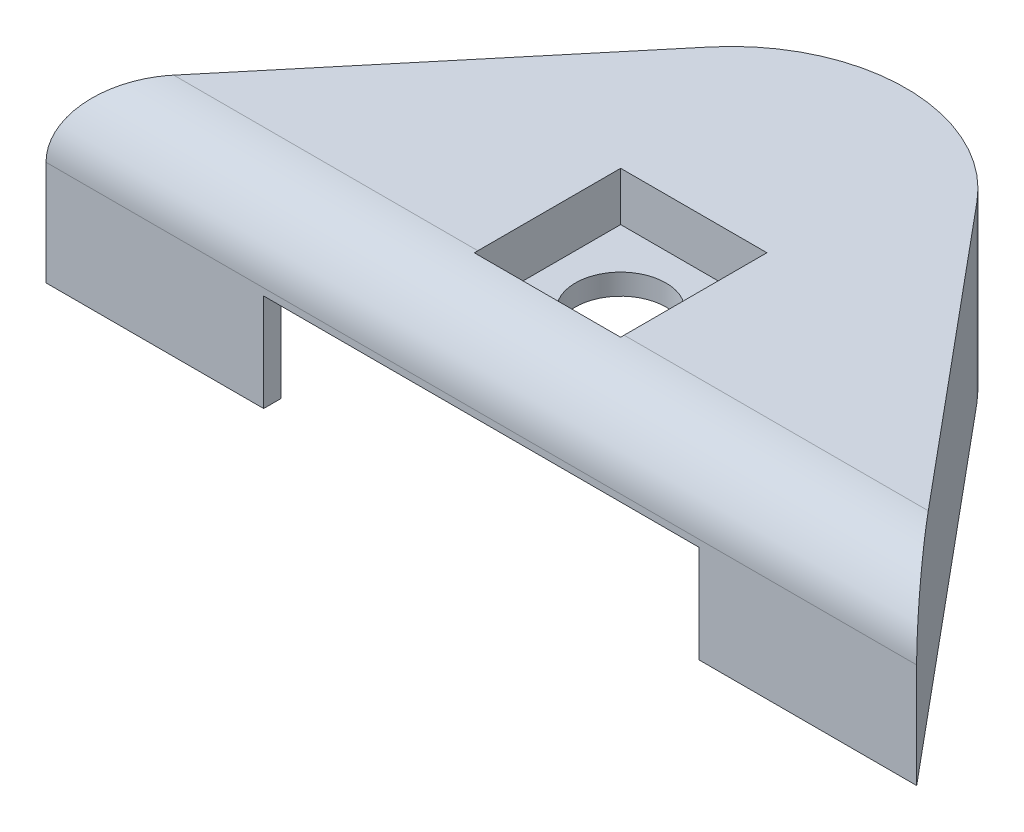
SolidWorks part; units mm, degrees
ref_plane "Ebene vorne" through (0, 0, 0) normal (0, 0, 1) x (1, 0, 0)
ref_plane "Ebene oben" through (0, 0, 0) normal (0, 1, 0) x (1, 0, 0)
ref_plane "Ebene rechts" through (0, 0, 0) normal (1, 0, 0) x (0, 0, -1)
sketch "Skizze1" plane through (0, 0, 0) normal (0, 1, 0) x (1, 0, 0)
  line L0 (-125, -75) -> (-38.4111, 28.9067)
  line L1 (-125, -75) -> (125, -75)
  line L2 (-125, -75) -> (-125, 75)
  line L3 (-125, 75) -> (125, 75)
  line L4 (125, -75) -> (125, 75)
  line L5 (-125, -75) -> (125, 75) construction
  line L6 (-125, 75) -> (125, -75) construction
  line L7 (38.4111, 28.9067) -> (125, -75)
  arc A0 (-38.4111, 28.9067) -> (38.4111, 28.9067) centre (0, -3.1025) cw
  point P0 (0, 0)
  point P9 (0, 75)
  dimension "D3" = 50
  dimension "D1" = 250
  dimension "D2" = 150
extrude "Aufsatz-Linear austragen1" add sketch "Skizze1" along normal blind 50 contours A0 L0 L1 L7 region at (0, 0, 28.5578)
sketch "Skizze2" plane through (0, 0, 75) normal (0, 0, 1) x (1, 0, 0)
  line L1 (-62.5, 28) -> (62.5, 28)
  line L7 (-62.5, 28) -> (-62.5, 0)
  line L9 (-125, 0) -> (125, 0) construction
  line L10 (-62.5, 0) -> (62.5, 0)
  line L11 (62.5, 0) -> (62.5, 28)
  point P3 (0, 28)
  point P5 (0, 28)
extrude "Schnitt-Linear austragen1" cut sketch "Skizze2" against normal blind 30
sketch "Skizze3" plane through (0, 0, 0) normal (0, -1, 0) x (1, 0, 0)
  line L11 (114.3248, 70) -> (-114.3248, 70)
  line L12 (-125, 75) -> (-62.5, 75) construction
  line L16 (-114.3248, 70) -> (-34.57, -25.7058)
  line L17 (34.57, -25.7058) -> (114.3248, 70)
  line L18 (-125, 75) -> (-38.4111, -28.9067) construction
  line L19 (38.4111, -28.9067) -> (125, 75) construction
  arc A0 (-34.57, -25.7058) -> (34.57, -25.7058) centre (0, 3.1025) ccw
  dimension "D4" = 45
  dimension "D1" = 5
  dimension "D2" = 5
  dimension "D3" = 5
extrude "Schnitt-Linear austragen2" cut sketch "Skizze3" against normal blind 30 contours L17 L11 L16 A0
sketch "Skizze4" plane through (0, 50, 0) normal (0, 1, 0) x (1, 0, 0)
  circle A1 centre (0, -35) radius 13
  dimension "D1" = 26
  dimension "D2" = 35
extrude "Schnitt-Linear austragen3" cut sketch "Skizze4" against normal blind 30
sketch "Skizze5" plane through (0, 50, 0) normal (0, 1, 0) x (1, 0, 0)
  line L5 (-21, -56) -> (21, -56)
  line L6 (-21, -56) -> (-21, -14)
  line L7 (-21, -14) -> (21, -14)
  line L8 (21, -56) -> (21, -14)
  line L9 (-21, -56) -> (21, -14) construction
  line L10 (-21, -14) -> (21, -56) construction
  point P0 (0, -35)
  dimension "D1" = 42
  dimension "D2" = 42
extrude "Schnitt-Linear austragen4" cut sketch "Skizze5" against normal offset from surface (14 mm away) 6 up to face at (0, 30, 22)
fillet "Verrundung1" radius 20 1 edges at (0, 50, 75)
